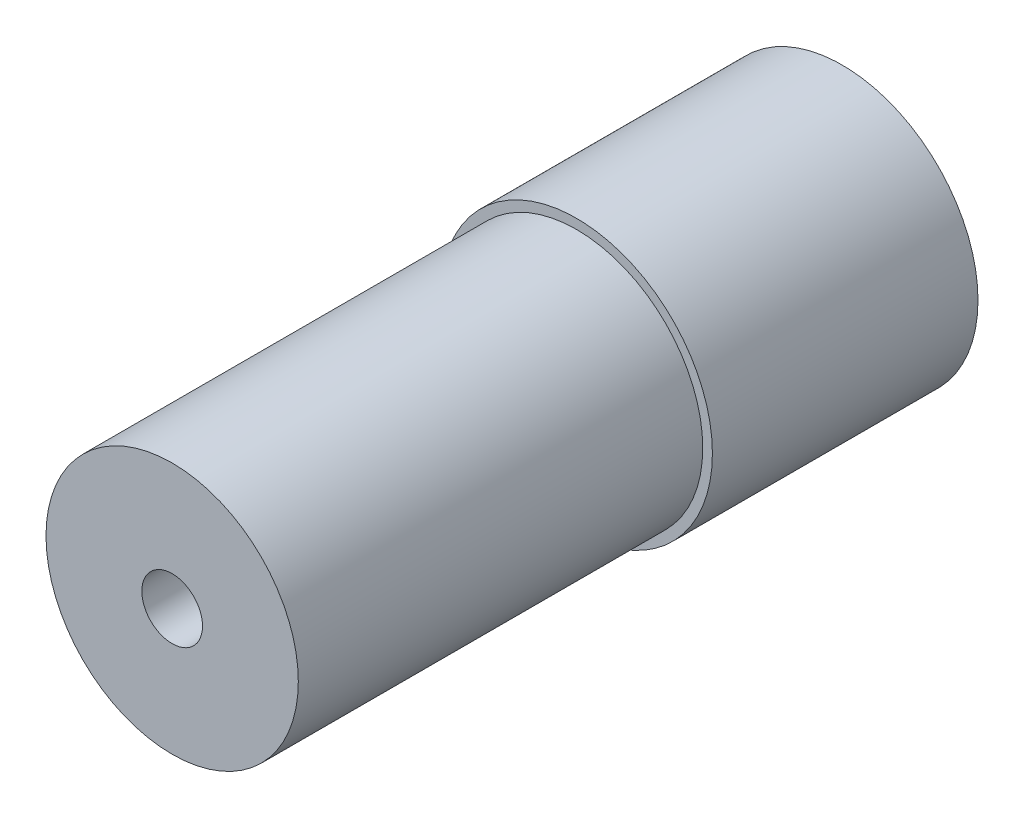
SolidWorks part; units mm, degrees
ref_plane "Front Plane" through (0, 0, 0) normal (0, 0, 1) x (1, 0, 0)
ref_plane "Top Plane" through (0, 0, 0) normal (0, 1, 0) x (1, 0, 0)
ref_plane "Right Plane" through (0, 0, 0) normal (1, 0, 0) x (0, 0, -1)
sketch "Sketch1" plane through (0, 0, 0) normal (0, 0, 1) x (1, 0, 0)
  circle A0 centre (0, 0) radius 22.5
  circle A1 centre (0, 0) radius 20.9
  dimension "D1" = 45
  dimension "D2" = 41.8
extrude "Boss-Extrude1" add sketch "Sketch1" along normal blind 44
extrude "Boss-Extrude2" add sketch "Sketch1<2>" along normal blind 111 contours A1
sketch "Sketch1<2>" plane through (0, 0, 0) normal (0, 0, 1) x (1, 0, 0) same geometry as "Sketch1"
sketch "Sketch2" plane through (0, 0, 0) normal (0, 0, -1) x (-1, 0, 0)
  circle A0 centre (0, 0) radius 13
  circle A1 centre (0, 0) radius 5
  dimension "D1" = 26
  dimension "D2" = 10
sketch "Sketch3" plane through (0, 0, 0) normal (0, 0, -1) x (-1, 0, 0)
  circle A0 centre (0, 0) radius 5.025
  dimension "D1" = 10.05
extrude "Cut-Extrude1" cut sketch "Sketch3" against normal blind 171 contours A0
extrude "Boss-Extrude5" add sketch "Sketch2" along normal blind 2 contours A0
extrude "Cut-Extrude2" cut sketch "Sketch2<4>" along normal blind 35 contours A1
sketch "Sketch2<4>" plane through (0, 0, 0) normal (0, 0, -1) x (-1, 0, 0) same geometry as "Sketch2"
sketch "Sketch6" plane through (0, 0, -2) normal (0, 0, -1) x (-1, 0, 0)
  line L0 (0, 0) -> (17.5, 0) construction
  line L1 (0, 0) -> (12.3744, 12.3744) construction
  circle A0 centre (17.5, 0) radius 1.5
  circle A1 centre (12.3744, 12.3744) radius 4.5
  circle A2 centre (12.3744, 12.3744) radius 3.25
  circle A3 centre (12.3744, -12.3744) radius 3.25
  circle A4 centre (12.3744, -12.3744) radius 4.5
  circle A5 centre (0, -17.5) radius 1.5
  circle A6 centre (-12.3744, -12.3744) radius 3.25
  circle A7 centre (-12.3744, -12.3744) radius 4.5
  circle A8 centre (-17.5, 0) radius 1.5
  circle A9 centre (-12.3744, 12.3744) radius 3.25
  circle A10 centre (-12.3744, 12.3744) radius 4.5
  circle A11 centre (0, 17.5) radius 1.5
  point P25 (0, 0)
  dimension "D1" = 45
  dimension "D2" = 9
  dimension "D3" = 4
  dimension "D4" = 17.5
  dimension "D5" = 17.5
  dimension "D6" = 17.5
extrude "Cut-Extrude4" cut sketch "Sketch6" against normal blind 10 contours A11
extrude "Cut-Extrude5" cut sketch "Sketch6<3>" against normal blind 10 contours A0
sketch "Sketch6<3>" plane through (0, 0, -2) normal (0, 0, -1) x (-1, 0, 0) same geometry as "Sketch6"
extrude "Cut-Extrude6" cut sketch "Sketch6<4>" against normal blind 10 contours A5
sketch "Sketch6<4>" plane through (0, 0, -2) normal (0, 0, -1) x (-1, 0, 0) same geometry as "Sketch6"
extrude "Cut-Extrude7" cut sketch "Sketch6<5>" against normal blind 10 contours A8
sketch "Sketch6<5>" plane through (0, 0, -2) normal (0, 0, -1) x (-1, 0, 0) same geometry as "Sketch6"
extrude "Cut-Extrude8" cut sketch "Sketch6<7>" against normal blind 4 contours A1
sketch "Sketch6<7>" plane through (0, 0, -2) normal (0, 0, -1) x (-1, 0, 0) same geometry as "Sketch6"
extrude "Cut-Extrude9" cut sketch "Sketch6<8>" against normal blind 4 contours A10
sketch "Sketch6<8>" plane through (0, 0, -2) normal (0, 0, -1) x (-1, 0, 0) same geometry as "Sketch6"
extrude "Cut-Extrude10" cut sketch "Sketch6<9>" against normal blind 4 contours A7
sketch "Sketch6<9>" plane through (0, 0, -2) normal (0, 0, -1) x (-1, 0, 0) same geometry as "Sketch6"
extrude "Cut-Extrude11" cut sketch "Sketch6<10>" against normal blind 4 contours A4
sketch "Sketch6<10>" plane through (0, 0, -2) normal (0, 0, -1) x (-1, 0, 0) same geometry as "Sketch6"
